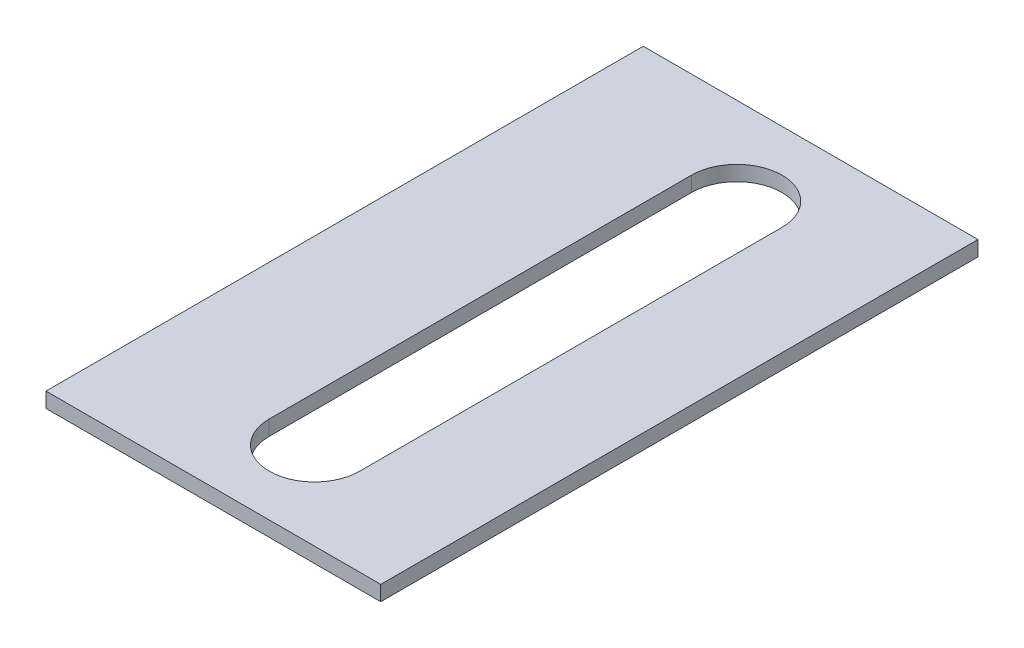
SolidWorks part; units mm, degrees
ref_plane "Front Plane" through (0, 0, 0) normal (0, 0, 1) x (1, 0, 0)
ref_plane "Top Plane" through (0, 0, 0) normal (0, 1, 0) x (1, 0, 0)
ref_plane "Right Plane" through (0, 0, 0) normal (1, 0, 0) x (0, 0, -1)
sketch "Sketch1" plane through (0, 0, 0) normal (1, 0, 0) x (0, 0, -1)
  line L1 (-6.9, -4.4) -> (6.9, -4.4)
  line L2 (-6.9, -4.4) -> (-6.9, 4.4)
  line L3 (-6.9, 4.4) -> (6.9, 4.4)
  line L4 (6.9, -4.4) -> (6.9, 4.4)
  line L5 (-6.9, -4.4) -> (6.9, 4.4) construction
  line L6 (-6.9, 4.4) -> (6.9, -4.4) construction
  point P0 (0, 0)
  dimension "D1" = 13.8
  dimension "D2" = 8.8
extrude "Boss-Extrude1" add sketch "Sketch1" along normal blind 3
sketch "Sketch2" plane through (3, 0, 0) normal (1, 0, 0) x (0, 0, -1)
  line L0 (6.9, 4.4) -> (-6.9, 4.4) construction
  line L1 (1, 4.4) -> (-1, 4.4)
  line L2 (1, 4.4) -> (1, -30.6)
  line L3 (1, -30.6) -> (-1, -30.6)
  line L4 (-1, 4.4) -> (-1, -30.6)
  line L5 (-6.9, -4.4) -> (6.9, -4.4) construction
  line L6 (-6.9, -4.4) -> (6.9, -4.4) construction
  point P8 (0, -4.4)
  point P9 (0, -30.6)
  dimension "D1" = 2
  dimension "D2" = 26.2
extrude "Boss-Extrude2" add sketch "Sketch2" along normal blind 3
sketch "Sketch3" plane through (6, 0, 0) normal (1, 0, 0) x (0, 0, -1)
  line L1 (-0.6, -30.6) -> (0.6, -30.6)
  line L2 (-0.6, -30.6) -> (-0.6, -24.6)
  line L3 (-0.6, -24.6) -> (0.6, -24.6)
  line L4 (0.6, -30.6) -> (0.6, -24.6)
  line L5 (-1, -30.6) -> (1, -30.6) construction
  point P10 (0, -30.6)
  point P11 (0, -30.6)
  dimension "D1" = 1.2
  dimension "D2" = 6
extrude "Boss-Extrude3" add sketch "Sketch3" along normal blind 7
fillet "Fillet3" radius 10 1 edges at (3, -4.4, 0)
sketch "Sketch5" plane through (0, 4.4, 0) normal (0, 1, 0) x (1, 0, 0)
  line L0 (3, 6.9) -> (0, 6.9) construction
  line L1 (3, -6.9) -> (-12, -6.9)
  line L2 (3, -6.9) -> (3, 6.9)
  line L3 (3, 6.9) -> (-12, 6.9)
  line L4 (-12, -6.9) -> (-12, 6.9)
  dimension "D1" = 15
extrude "Boss-Extrude4" add sketch "Sketch5" along normal blind 4
sketch "Sketch6" plane through (0, 4.4, 0) normal (0, -1, 0) x (1, 0, 0)
  line L0 (-6, 3) -> (-6, -3) construction
  line L1 (0, -6.9) -> (0, 6.9) construction
  circle A0 centre (-6, 3) radius 1.5
  circle A1 centre (-6, -3) radius 1.5
  point P4 (0, 0)
  point P7 (-6, 0)
  dimension "D1" = 3
  dimension "D2" = 6
  dimension "D3" = 6
extrude "Cut-Extrude4" cut sketch "Sketch6" against normal through all
sketch "Sketch8" plane through (0, 0, -1) normal (0, 0, -1) x (-1, 0, 0)
  line L0 (-3, -18.7582) -> (0, -4.4)
  line L1 (-3, -30.6) -> (-3, -11.5414) construction
  line L2 (0, -4.4) -> (-3, -4.4)
  line L3 (-3, -4.4) -> (-3, -18.7582)
extrude "Boss-Extrude5" add sketch "Sketch8" against normal up to surface (2 mm away) up to face at (3.5314, -10.3485, 1)
chamfer "Chamfer2" distance 3 angle 45 1 edges at (3, 4.4, 0)
sketch "Sketch11" plane through (0, 0, -0.6) normal (0, 0, -1) x (-1, 0, 0)
  line L0 (-6, -24.6) -> (-13, -24.6)
  line L1 (-13, -24.6) -> (-6, 1.7425)
  line L2 (-6, 1.7425) -> (-6, -24.6)
extrude "Boss-Extrude7" add sketch "Sketch11" against normal up to surface (1.2 mm away) up to face at (9.5, -27.6, 0.6)
sketch "Sketch12" plane through (0, 0, -6.9) normal (0, 0, -1) x (-1, 0, 0)
  line L0 (-3, -4.4) -> (-3, 8.4) construction
  line L1 (12, 8.4) -> (-3, 8.4)
  line L2 (12, 8.4) -> (12, 4.4)
  line L3 (12, 4.4) -> (-3, 4.4)
  line L4 (-3, 8.4) -> (-3, 4.4)
  line L5 (0, 4.4) -> (12, 4.4) construction
extrude "Boss-Extrude8" add sketch "Sketch12" along normal blind 3
sketch "Sketch13" plane through (0, 0, 6.9) normal (0, 0, 1) x (1, 0, 0)
  line L0 (3, 8.4) -> (3, -4.4) construction
  line L1 (-12, 8.4) -> (3, 8.4)
  line L2 (-12, 8.4) -> (-12, 4.4)
  line L3 (-12, 4.4) -> (3, 4.4)
  line L4 (3, 8.4) -> (3, 4.4)
  line L5 (-12, 4.4) -> (0, 4.4) construction
extrude "Boss-Extrude9" add sketch "Sketch13" along normal blind 3
sketch "Sketch14" plane through (0, 8.4, 0) normal (0, 1, 0) x (1, 0, 0)
  line L0 (-6, 3) -> (-6, -3) construction
  line L2 (-7.5, 7) -> (-7.5, -7)
  line L4 (-4.5, 7) -> (-4.5, -7)
  arc A0 (-7.5, 7) -> (-4.5, 7) centre (-6, 7) cw
  arc A1 (-4.5, -7) -> (-7.5, -7) centre (-6, -7) cw
  point P8 (-6, 0)
  point P10 (-4.5, 0)
  dimension "D1" = 3
  dimension "D2" = 14
extrude "Cut-Extrude7" cut sketch "Sketch14" against normal through all both and the other way through all
sketch "Sketch15" plane through (0, -30.6, 0) normal (0, -1, 0) x (1, 0, 0)
  line L0 (13, 0.6) -> (13, -0.6) construction
  line L1 (13, 0.32) -> (12.1921, 0.32)
  line L2 (13, 0.32) -> (13, -0.32)
  line L3 (13, -0.32) -> (12.1921, -0.32)
  line L4 (12.1921, 0.32) -> (12.1921, -0.32)
  line L5 (11.9922, 0.6) -> (11.9922, -0.6) construction
  line L6 (13, 0.6) -> (6, 0.6) construction
  line L7 (13, -0.6) -> (6, -0.6) construction
  point P13 (13, 0)
  point P14 (11.9922, 0)
  dimension "D1" = 0.28
extrude "Cut-Extrude8" cut sketch "Sketch15" against normal through all both and the other way through all
sketch "Sketch16" plane through (12.1921, 0, 0) normal (1, 0, 0) x (0, 0, -1)
  line L0 (0.32, -21.5597) -> (0.32, -30.6) construction
  line L1 (-0.32, -30.6) -> (0.32, -30.6)
  line L2 (-0.32, -30.6) -> (-0.32, -30)
  line L3 (-0.32, -30) -> (0.32, -30)
  line L4 (0.32, -30.6) -> (0.32, -30)
  dimension "D1" = 0.6
extrude "Cut-Extrude9" cut sketch "Sketch16" against normal through all both and the other way through all
chamfer "Chamfer3" distance 1 angle 45 1 edges at (12.1921, -30, 0)
sketch "Sketch17" plane through (0, 4.4, 0) normal (0, -1, 0) x (1, 0, 0)
  line L1 (20.8467, 21.9752) -> (-20.8467, 21.9752)
  line L2 (20.8467, 21.9752) -> (20.8467, -21.9752)
  line L3 (20.8467, -21.9752) -> (-20.8467, -21.9752)
  line L4 (-20.8467, 21.9752) -> (-20.8467, -21.9752)
  line L5 (20.8467, 21.9752) -> (-20.8467, -21.9752) construction
  line L6 (20.8467, -21.9752) -> (-20.8467, 21.9752) construction
sketch "Sketch18" plane through (0, 0, 9.9) normal (0, 0, 1) x (1, 0, 0)
  line L0 (3, 8.4) -> (-12, 8.4) construction
  line L1 (-0.9029, 8.4) -> (19.7991, 8.4)
  line L2 (-0.9029, 8.4) -> (-0.9029, -33.328)
  line L3 (-0.9029, -33.328) -> (19.7991, -33.328)
  line L4 (19.7991, 8.4) -> (19.7991, -33.328)
extrude "Cut-Extrude10" cut sketch "Sketch18" against normal blind 36
sketch "Sketch19" plane through (0, 4.4, 0) normal (0, -1, 0) x (1, 0, 0)
  line L0 (-0.9029, -9.9) -> (-0.9029, 9.9) construction
  line L1 (-12, -9.9) -> (-0.9029, -9.9)
  line L2 (-12, -9.9) -> (-12, 11.0285)
  line L3 (-12, 11.0285) -> (-0.9029, 11.0285)
  line L4 (-0.9029, -9.9) -> (-0.9029, 11.0285)
extrude "Cut-Extrude11" cut sketch "Sketch19" against normal blind 3.5
